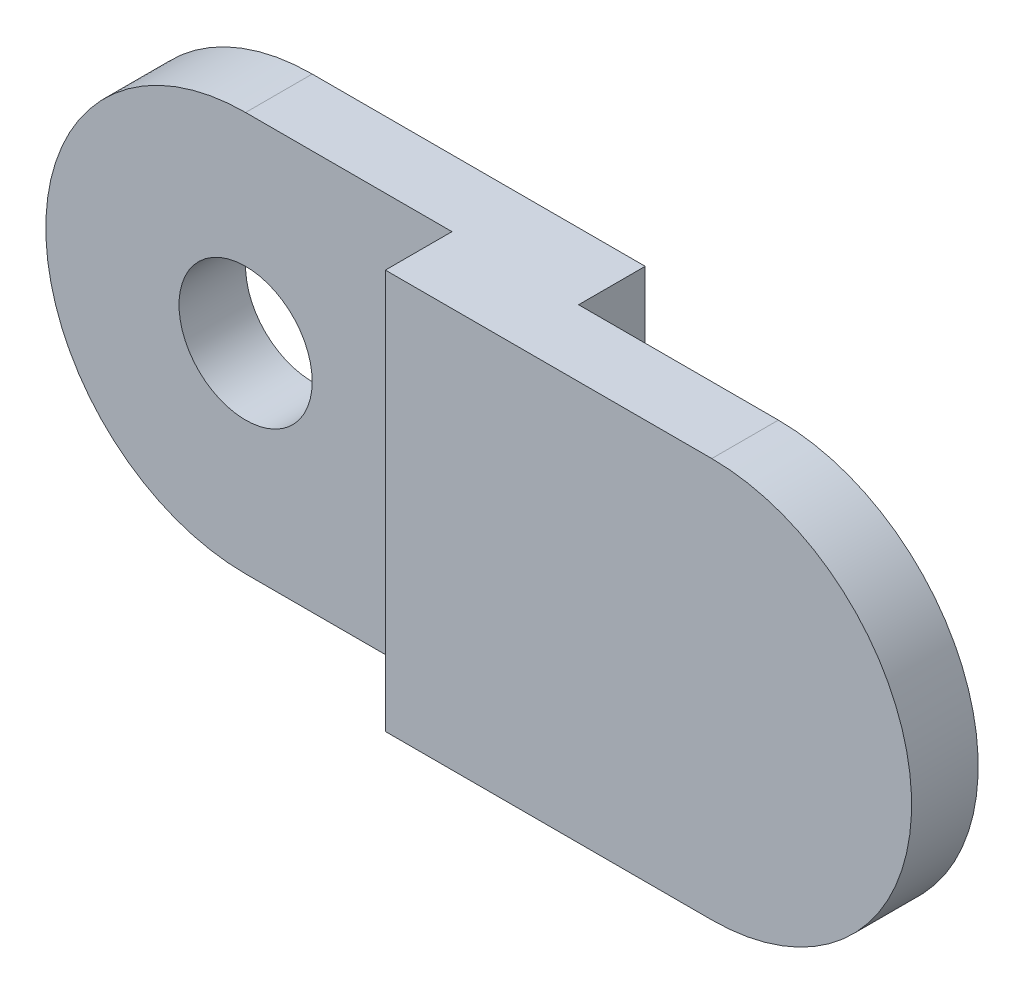
SolidWorks part; units mm, degrees
ref_plane "Front Plane" through (0, 0, 0) normal (0, 0, 1) x (1, 0, 0)
ref_plane "Top Plane" through (0, 0, 0) normal (0, 1, 0) x (1, 0, 0)
ref_plane "Right Plane" through (0, 0, 0) normal (1, 0, 0) x (0, 0, -1)
sketch "Sketch1" plane through (0, 0, 0) normal (0, 0, 1) x (1, 0, 0)
  line L1 (0, 0) -> (20, 0)
  line L3 (0, 15) -> (20, 15)
  arc A0 (0, 15) -> (0, 0) centre (0, 7.5) ccw
  arc A1 (0, 0) -> (-3.4224, 0.8264) centre (0, 7.5) cw
  arc A2 (20, 15) -> (20, 0) centre (20, 7.5) cw
  dimension "D1" = 20
  dimension "D2" = 15
extrude "Boss-Extrude1" add sketch "Sketch1" along normal blind 5 contours A0 | L1 L3 region at (10, 7.5, 0)
sketch "Sketch6" plane through (0, 0, 0) normal (0, 0, -1) x (-1, 0, 0)
  line L0 (0, 0) -> (-20, 0) construction
  line L1 (0, 0) -> (-20, 0) construction
  line L2 (-20, 15) -> (-12.5, 15)
  line L8 (-20, 0) -> (-12.5, 0)
  line L9 (-12.5, 15) -> (-12.5, 0)
  arc A0 (-20, 15) -> (-20, 0) centre (-20, 7.5) ccw
extrude "Cut-Extrude2" cut sketch "Sketch6" against normal blind 2.5
sketch "Sketch7" plane through (0, 0, 5) normal (0, 0, 1) x (1, 0, 0)
  line L0 (0, 0) -> (20, 0) construction
  line L1 (0, 0) -> (20, 0) construction
  line L2 (0, 15) -> (7.7468, 15)
  line L4 (0, 0) -> (5, 0)
  line L5 (0, 0) -> (7.7468, 0)
  line L6 (7.7468, 15) -> (7.7468, 0)
  arc A0 (0, 15) -> (0, 0) centre (0, 7.5) ccw
  arc M1 (0, 15) -> (0, 0) centre (0, 7.5) ccw
extrude "Cut-Extrude6" cut sketch "Sketch7" against normal blind 2.5 contours M1 region at (0.8254, 7.5, 5)
sketch "Sketch11" plane through (0, 0, 2.5) normal (0, 0, 1) x (1, 0, 0)
  circle A0 centre (0, 7.5) radius 2.5
  dimension "D1" = 5
extrude "Cut-Extrude7" cut sketch "Sketch11" against normal blind 2.5
sketch "Sketch12" plane through (0, 0, 2.5) normal (0, 0, -1) x (-1, 0, 0)
  circle A0 centre (-20, 7.5) radius 2.5
  dimension "D1" = 5
extrude "Boss-Extrude3" add sketch "Sketch12" along normal blind 2.5 contours A0
